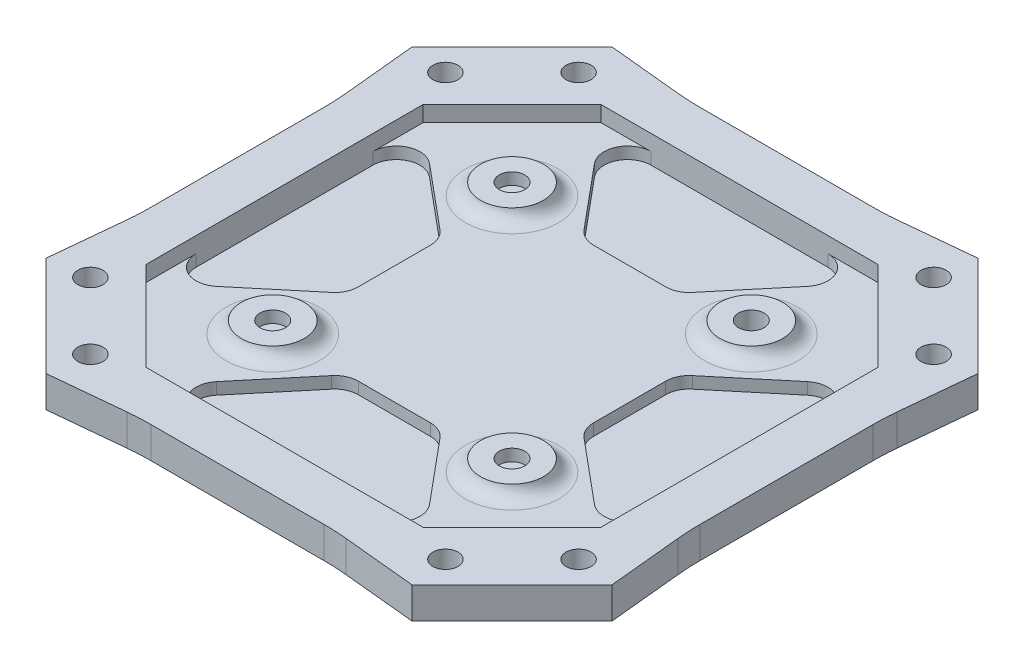
SolidWorks part; units mm, degrees
ref_plane "Front Plane" through (0, 0, 0) normal (0, 0, 1) x (1, 0, 0)
ref_plane "Top Plane" through (0, 0, 0) normal (0, 1, 0) x (1, 0, 0)
ref_plane "Right Plane" through (0, 0, 0) normal (1, 0, 0) x (0, 0, -1)
sketch "Sketch1" plane through (0, 0, 0) normal (0, 1, 0) x (1, 0, 0)
  line L0 (0, 0) -> (84.8528, 84.8528) construction
  line L1 (-35, 35) -> (35, 35) construction
  line L2 (-35, 35) -> (-35, -35) construction
  line L3 (-35, -35) -> (35, -35) construction
  line L4 (35, 35) -> (35, -35) construction
  line L5 (-35, 35) -> (35, -35) construction
  line L6 (-35, -35) -> (35, 35) construction
  line L7 (0, 35) -> (0, -35) construction
  line L8 (-12.5, 35) -> (12.5, 35)
  line L9 (35, 12.5) -> (35, -12.5)
  line L10 (12.5, -35) -> (-12.5, -35)
  line L11 (-35, -12.5) -> (-35, 12.5)
  line L12 (20.5061, 33.234) -> (33.234, 20.5061) construction
  line L13 (23.3345, 36.0624) -> (36.0624, 23.3345)
  line L14 (12.5, 35) -> (23.3345, 36.0624)
  line L15 (35, 12.5) -> (36.0624, 23.3345)
  line L16 (35, -12.5) -> (36.0624, -23.3345)
  line L17 (36.0624, -23.3345) -> (23.3345, -36.0624)
  line L18 (12.5, -35) -> (23.3345, -36.0624)
  line L19 (-12.5, -35) -> (-23.3345, -36.0624)
  line L20 (-23.3345, -36.0624) -> (-36.0624, -23.3345)
  line L21 (-35, -12.5) -> (-36.0624, -23.3345)
  line L22 (-35, 12.5) -> (-36.0624, 23.3345)
  line L23 (-36.0624, 23.3345) -> (-23.3345, 36.0624)
  line L24 (-12.5, 35) -> (-23.3345, 36.0624)
  circle A0 centre (22.6274, 31.1127) radius 1.6
  circle A1 centre (31.1127, 22.6274) radius 1.6
  circle A2 centre (22.6274, -31.1127) radius 1.6
  circle A3 centre (31.1127, -22.6274) radius 1.6
  circle A4 centre (-31.1127, -22.6274) radius 1.6
  circle A5 centre (-22.6274, -31.1127) radius 1.6
  circle A6 centre (-22.6274, 31.1127) radius 1.6
  circle A7 centre (-31.1127, 22.6274) radius 1.6
  point P0 (0, 0)
  point P21 (0, 0)
  point P54 (0, 0)
  dimension "D12" = 3.2
  dimension "D1" = 70
  dimension "D2" = 70
  dimension "D3" = 120
  dimension "D4" = 25
  dimension "D5" = 12.5
  dimension "D7" = 18
  dimension "D8" = 9
  dimension "D9" = 82
  dimension "D10" = 4
  dimension "D11" = 18
  dimension "D13" = 6
  dimension "D14" = 6
  dimension "D6" = 4
  dimension "D15" = 4
extrude "Boss-Extrude2" add sketch "Sketch1" along normal blind 4
sketch "Sketch2" plane through (0, 4, 0) normal (0, 1, 0) x (1, 0, 0)
  line L0 (0, 35) -> (0, 0) construction
  line L1 (12.5, 35) -> (-12.5, 35) construction
  line L2 (0, 0) -> (-35, 0) construction
  line L3 (-35, 12.5) -> (-35, -12.5) construction
  line L4 (-17.669, 29) -> (17.669, 29)
  line L5 (17.669, 29) -> (29, 17.669)
  line L6 (29, 17.669) -> (29, -17.669)
  line L7 (29, -17.669) -> (17.669, -29)
  line L8 (17.669, -29) -> (-17.669, -29)
  line L9 (-17.669, -29) -> (-29, -17.669)
  line L10 (-29, -17.669) -> (-29, 17.669)
  line L11 (-29, 17.669) -> (-17.669, 29)
  line L12 (-12.5, -35) -> (12.5, -35) construction
  line L13 (-36.0624, -23.3345) -> (-23.3345, -36.0624) construction
  line L18 (35, -12.5) -> (35, 12.5) construction
  line L21 (36.0624, 23.3345) -> (23.3345, 36.0624) construction
  line L22 (-23.3345, 36.0624) -> (-36.0624, 23.3345) construction
  line L23 (23.3345, -36.0624) -> (36.0624, -23.3345) construction
  dimension "D1" = 6
  dimension "D2" = 9
  dimension "D3" = 6
  dimension "D4" = 6
  dimension "D5" = 9
extrude "Cut-Extrude1" cut sketch "Sketch2" against normal blind 2
sketch "Sketch3" plane through (0, 2, 0) normal (0, 1, 0) x (1, 0, 0)
  line L0 (0, 29) -> (0, 0) construction
  line L1 (17.669, 29) -> (-17.669, 29) construction
  line L2 (0, 0) -> (-29, 0) construction
  line L3 (-29, 17.669) -> (-29, -17.669) construction
  line L4 (-24.0792, 13.5676) -> (-16.0792, 6.8995)
  line L5 (-15, 4.5951) -> (-15, -4.5951)
  line L6 (-16.0792, -6.8995) -> (-24.0792, -13.5676)
  line L7 (-29, -11.2631) -> (-29, 11.2631)
  line L8 (13.5676, 24.0792) -> (6.8995, 16.0792)
  line L9 (-11.2631, 29) -> (11.2631, 29)
  line L10 (-6.8995, 16.0792) -> (-13.5676, 24.0792)
  line L11 (4.5951, 15) -> (-4.5951, 15)
  line L12 (24.0792, -13.5676) -> (16.0792, -6.8995)
  line L13 (29, 11.2631) -> (29, -11.2631)
  line L14 (16.0792, 6.8995) -> (24.0792, 13.5676)
  line L15 (15, -4.5951) -> (15, 4.5951)
  line L16 (-13.5676, -24.0792) -> (-6.8995, -16.0792)
  line L17 (11.2631, -29) -> (-11.2631, -29)
  line L18 (6.8995, -16.0792) -> (13.5676, -24.0792)
  line L19 (-4.5951, -15) -> (4.5951, -15)
  arc A0 (-24.0792, -13.5676) -> (-29, -11.2631) centre (-26, -11.2631) cw
  arc A1 (-15, -4.5951) -> (-16.0792, -6.8995) centre (-18, -4.5951) cw
  arc A2 (-16.0792, 6.8995) -> (-15, 4.5951) centre (-18, 4.5951) cw
  arc A3 (-24.0792, 13.5676) -> (-29, 11.2631) centre (-26, 11.2631) ccw
  arc A4 (13.5676, 24.0792) -> (11.2631, 29) centre (11.2631, 26) ccw
  arc A5 (-13.5676, 24.0792) -> (-11.2631, 29) centre (-11.2631, 26) cw
  arc A6 (-4.5951, 15) -> (-6.8995, 16.0792) centre (-4.5951, 18) cw
  arc A7 (6.8995, 16.0792) -> (4.5951, 15) centre (4.5951, 18) cw
  arc A8 (24.0792, -13.5676) -> (29, -11.2631) centre (26, -11.2631) ccw
  arc A9 (24.0792, 13.5676) -> (29, 11.2631) centre (26, 11.2631) cw
  arc A10 (15, 4.5951) -> (16.0792, 6.8995) centre (18, 4.5951) cw
  arc A11 (16.0792, -6.8995) -> (15, -4.5951) centre (18, -4.5951) cw
  arc A12 (-13.5676, -24.0792) -> (-11.2631, -29) centre (-11.2631, -26) ccw
  arc A13 (13.5676, -24.0792) -> (11.2631, -29) centre (11.2631, -26) cw
  arc A14 (4.5951, -15) -> (6.8995, -16.0792) centre (4.5951, -18) cw
  arc A15 (-6.8995, -16.0792) -> (-4.5951, -15) centre (-4.5951, -18) cw
  point P16 (-29, -17.669)
  point P19 (-15, -6)
  point P22 (-15, 6)
  point P25 (-29, 17.669)
  point P65 (0, 0)
  dimension "D3" = 3
  dimension "D1" = 15
  dimension "D2" = 12
  dimension "D4" = 4
extrude "Cut-Extrude2" cut sketch "Sketch3" against normal blind 1.5
sketch "Sketch4" plane through (0, 2, 0) normal (0, 1, 0) x (1, 0, 0)
  line L1 (0, 0) -> (15.25, 0) construction
  line L2 (0, 0) -> (0, 15.25) construction
  line L3 (0, 15.25) -> (15.25, 15.25) construction
  line L4 (15.25, 0) -> (15.25, 15.25) construction
  circle A0 centre (15.25, 15.25) radius 1.625
  dimension "D2" = 3.25
  dimension "D1" = 15.25
extrude "Cut-Extrude3" cut sketch "Sketch4" against normal through all
sketch "Sketch5" plane through (0, 2, 0) normal (0, 1, 0) x (1, 0, 0)
  circle A0 centre (15.25, 15.25) radius 4
  circle A1 centre (15.25, 15.25) radius 1.625 construction
  circle A2 centre (15.25, 15.25) radius 1.625
  dimension "D1" = 8
extrude "Boss-Extrude3" add sketch "Sketch5" along normal blind 1.5
ref_axis "Axis1" through (0, 4.2, 0) along (0, -1, 0)
pattern_circular "CirPattern1" count 4 over 360 about axis through (0, 4.2, 0) along (0, -1, 0) of "Boss-Extrude3"
fillet "Fillet1" radius 2 4 edges at (15.25, 2, -19.25) (15.25, 2, 11.25) (-15.25, 2, -19.25) (-15.25, 2, 11.25)
fillet "Fillet2" radius 30 8 edges at (35, 2, -12.5) (35, 2, 12.5) (12.5, 2, 35) (-12.5, 2, 35) (-35, 2, 12.5) (-35, 2, -12.5) (12.5, 2, -35) (-12.5, 2, -35)
